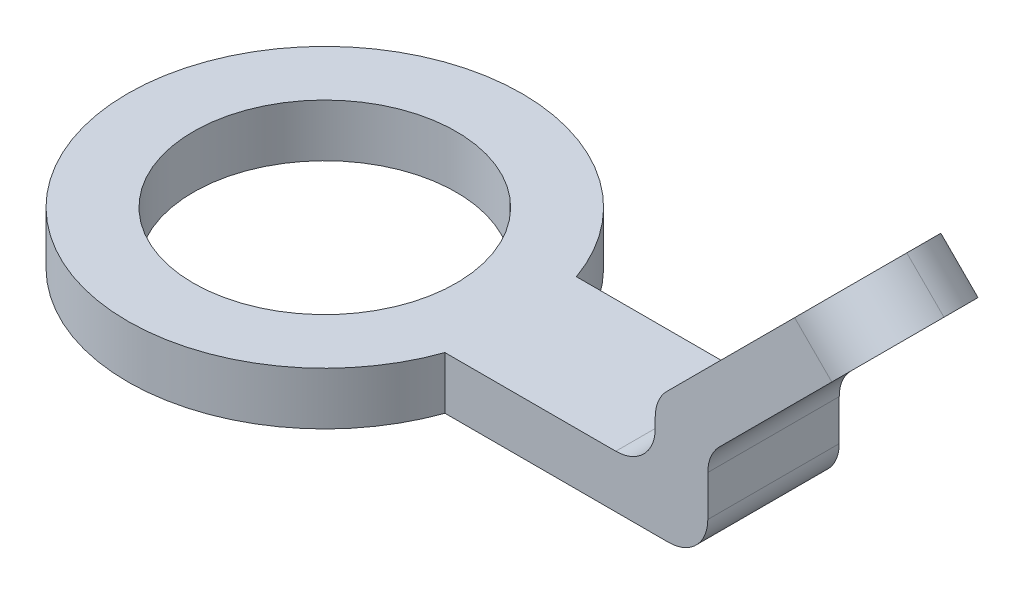
SolidWorks part; units mm, degrees
ref_plane "Front Plane" through (0, 0, 0) normal (0, 0, 1) x (1, 0, 0)
ref_plane "Top Plane" through (0, 0, 0) normal (0, 1, 0) x (1, 0, 0)
ref_plane "Right Plane" through (0, 0, 0) normal (1, 0, 0) x (0, 0, -1)
sketch "Sketch2" plane through (0, 0, 0) normal (0, 1, 0) x (1, 0, 0)
  line L0 (0, 0) -> (34.1421, 0) construction
  line L1 (34.1421, 5) -> (34.1421, -5)
  line L2 (34.1421, -5) -> (14.1421, -5)
  line L3 (34.1421, 5) -> (14.1421, 5)
  arc A0 (14.1421, 5) -> (14.1421, -5) centre (0, 0) ccw
  circle A1 centre (0, 0) radius 10
  dimension "D1" = 30
  dimension "D5" = 20
  dimension "D2" = 5
  dimension "D3" = 5
  dimension "D4" = 20
extrude "Boss-Extrude1" add sketch "Sketch2" along normal blind 4
sketch "Sketch3" plane through (0, 0, 5) normal (0, 0, 1) x (1, 0, 0)
  line L0 (34.1421, 4) -> (34.1421, 7.3431)
  line L1 (34.1421, 7.3431) -> (47.1127, 20.3137)
  line L2 (47.1127, 20.3137) -> (44.2843, 23.1421)
  line L3 (44.2843, 23.1421) -> (30.1421, 9)
  line L4 (30.1421, 9) -> (30.1421, 4)
  line L5 (14.1421, 4) -> (34.1421, 4) construction
  line L6 (30.1421, 4) -> (34.1421, 4)
  dimension "D1" = 4
  dimension "D2" = 4
  dimension "D3" = 135
  dimension "D4" = 5
  dimension "D5" = 20
extrude "Boss-Extrude2" add sketch "Sketch3" against normal blind 10
sketch "Sketch4" plane through (0, 0, 0) normal (0, -1, 0) x (1, 0, 0)
  circle A0 centre (0, 0) radius 12
  circle A1 centre (0, 0) radius 13
  dimension "D1" = 24
  dimension "D2" = 26
extrude "Boss-Extrude3" [suppressed] add sketch "Sketch4" along normal blind 1
fillet "Fillet1" radius 5 2 edges at (45.6985, 21.7279, -5) (45.6985, 21.7279, 5)
sketch "Sketch5" plane through (10.5711, -10.5711, 0) normal (-0.7071, 0.7071, 0) x (0.7071, 0.7071, 0)
  circle A0 centre (42.6777, 0) radius 2.5
  dimension "D1" = 5
hole_wizard "M3 Clearance Hole1" positions "Sketch6" profile "Sketch7" hole size "M3" standard "ANSI Metric" end condition through all
sketch "Sketch6" plane through (10.5711, -10.5711, 0) normal (-0.7071, 0.7071, 0) x (0.7071, 0.7071, 0)
  point P0 (42.6777, 0)
sketch "Sketch7" plane through (40.7487, 19.6066, 0) normal (0, 0, 1) x (-0.7071, -0.7071, 0)
  line L0 (0, 0) -> (0, 18.364)
  line L1 (0, 18.364) -> (1.8, 18.364)
  line L2 (1.8, 18.364) -> (1.8, 0)
  line L5 (1.8, 0) -> (0, 0)
  line L11 (0, -6.35) -> (0, 107.95) construction
  dimension "Thru Hole Dia." = 3.6
  dimension "Thru Hole Depth" = 18.364
fillet "Fillet2" radius 3 4 edges at (34.1421, 7.3431, 0) (30.1421, 9, 0) (34.1421, 0, 0) (30.1421, 4, 0)
